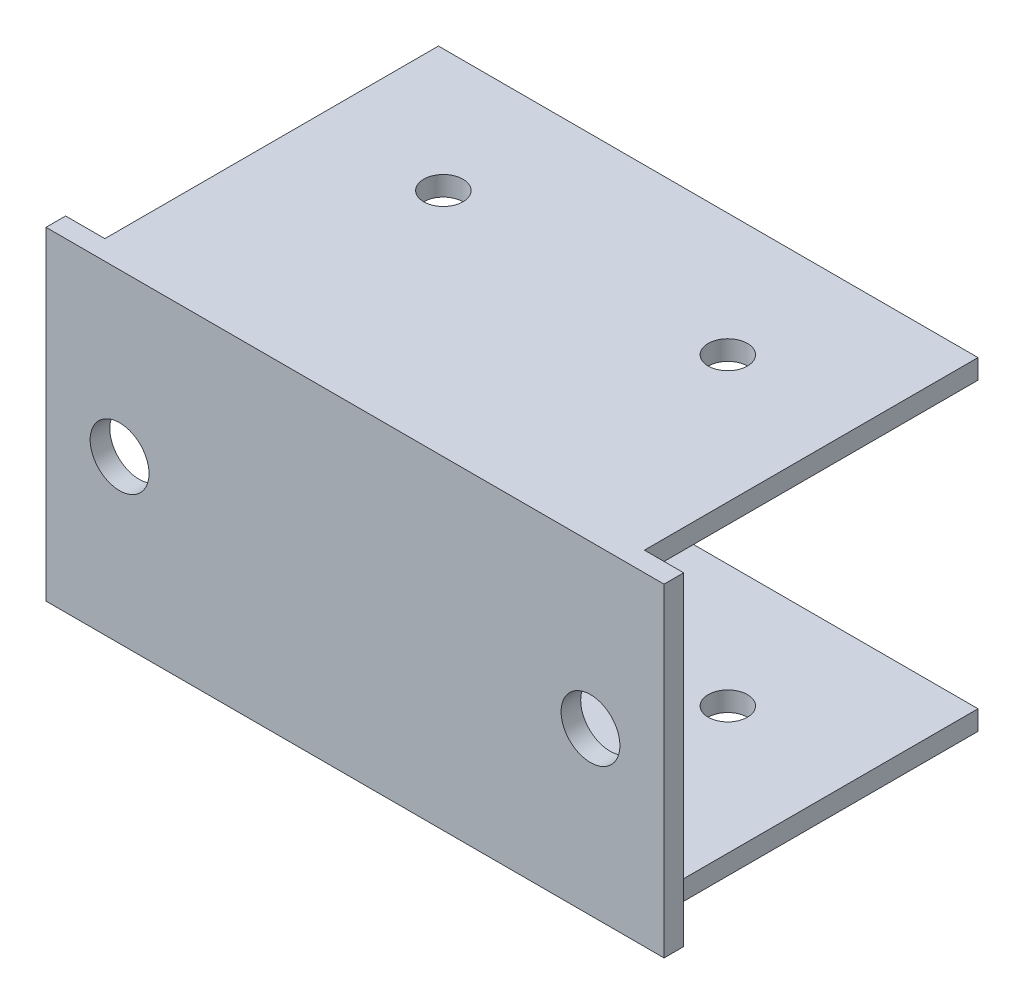
SolidWorks part; units mm, degrees
ref_plane "前视基准面" through (0, 0, 0) normal (0, 0, 1) x (1, 0, 0)
ref_plane "上视基准面" through (0, 0, 0) normal (0, 1, 0) x (1, 0, 0)
ref_plane "右视基准面" through (0, 0, 0) normal (1, 0, 0) x (0, 0, -1)
sketch "草图1" plane through (0, 0, 0) normal (0, 0, 1) x (1, 0, 0)
  line L1 (-31.5, 16.5) -> (31.5, 16.5)
  line L2 (-31.5, 16.5) -> (-31.5, -16.5)
  line L3 (-31.5, -16.5) -> (31.5, -16.5)
  line L4 (31.5, 16.5) -> (31.5, -16.5)
  line L5 (-31.5, 16.5) -> (31.5, -16.5) construction
  line L6 (-31.5, -16.5) -> (31.5, 16.5) construction
  point P0 (0, 0)
  dimension "D1" = 63
  dimension "D2" = 33
extrude "凸台-拉伸1" add sketch "草图1" along normal blind 2 contours L2 L3 L4 L1
sketch "草图2" plane through (0, 0, 2) normal (0, 0, 1) x (1, 0, 0)
  line L0 (-24, 0) -> (24, 0) construction
  circle A0 centre (-24, 0) radius 3
  circle A1 centre (24, 0) radius 3
  point P2 (0, 0)
  dimension "D2" = 6
  dimension "D3" = 6
  dimension "D1" = 48
extrude "切除-拉伸1" cut sketch "草图2" against normal blind 10
sketch "草图4" plane through (0, 16.5, 0) normal (0, 1, 0) x (1, 0, 0)
  line L0 (-31.5, -2) -> (31.5, -2) construction
  line L1 (-27.5, 34) -> (27.5, 34)
  line L2 (-27.5, 34) -> (-27.5, -2)
  line L3 (-27.5, -2) -> (27.5, -2)
  line L4 (27.5, 34) -> (27.5, -2)
  line L5 (-27.5, 34) -> (27.5, -2) construction
  line L6 (-27.5, -2) -> (27.5, 34) construction
  point P0 (0, 16)
  dimension "D1" = 36
  dimension "D2" = 55
extrude "凸台-拉伸2" add sketch "草图4" against normal blind 2
sketch "草图5" plane through (0, 16.5, 0) normal (0, 1, 0) x (1, 0, 0)
  line L0 (-14.5, 21.5) -> (14.5, 21.5) construction
  line L1 (27.5, 34) -> (-27.5, 34) construction
  circle A0 centre (-14.5, 21.5) radius 2
  circle A1 centre (14.5, 21.5) radius 2
  point P2 (0, 21.5)
  dimension "D3" = 4
  dimension "D4" = 4
  dimension "D1" = 12.5
  dimension "D2" = 29
extrude "切除-拉伸2" cut sketch "草图5" against normal through all
mirror "镜向1" about plane through (0, 0, 0) normal (0, 1, 0) of "切除-拉伸2", "凸台-拉伸2"
